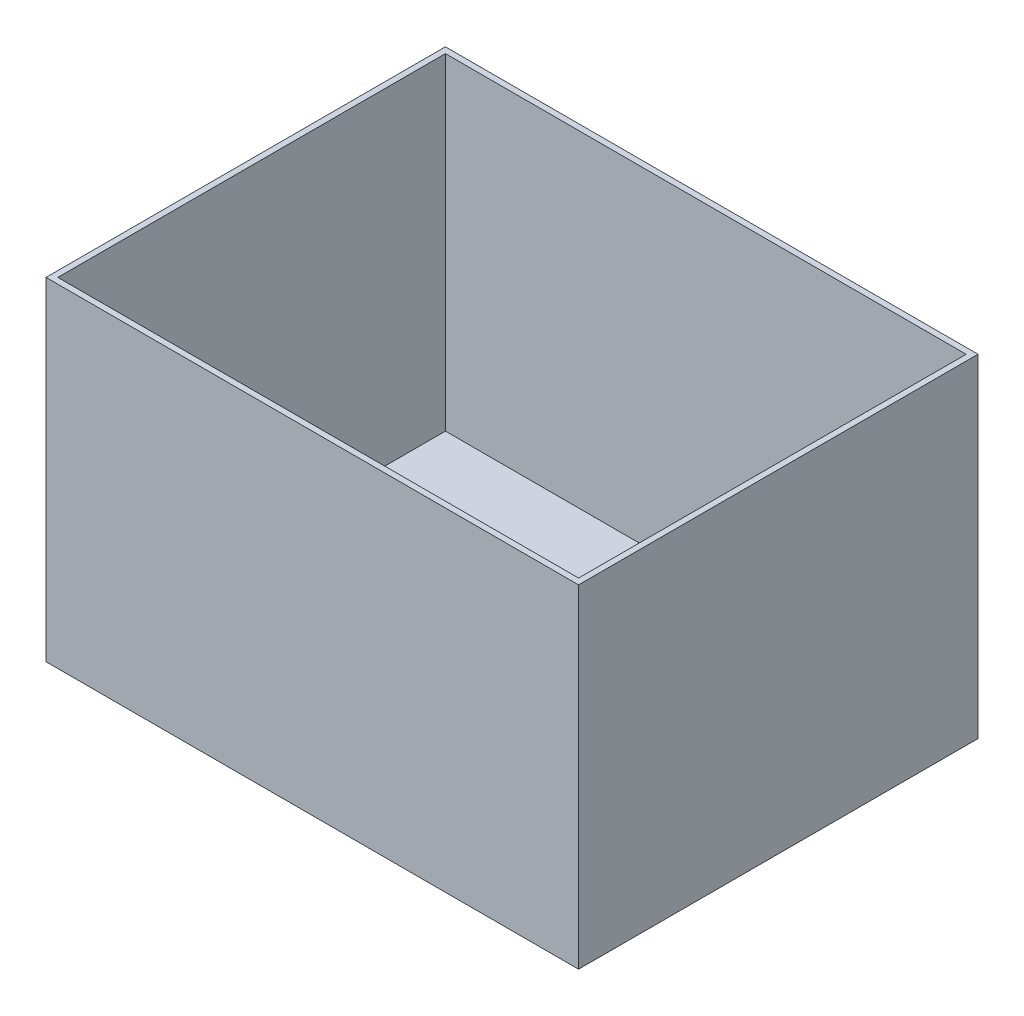
SolidWorks part; units mm, degrees
ref_plane "Alzado" through (0, 0, 0) normal (0, 0, 1) x (1, 0, 0)
ref_plane "Planta" through (0, 0, 0) normal (0, 1, 0) x (1, 0, 0)
ref_plane "Vista lateral" through (0, 0, 0) normal (1, 0, 0) x (0, 0, -1)
sketch "Croquis1" plane through (0, 0, 0) normal (0, 0, 1) x (1, 0, 0)
  line L1 (-180, 112.5) -> (180, 112.5)
  line L2 (-180, 112.5) -> (-180, -112.5)
  line L3 (-180, -112.5) -> (180, -112.5)
  line L4 (180, 112.5) -> (180, -112.5)
  line L5 (-180, 112.5) -> (180, -112.5) construction
  line L6 (-180, -112.5) -> (180, 112.5) construction
  point P0 (0, 0)
extrude "Saliente-Extruir1" add sketch "Croquis1" along normal blind 135 and the other way blind 135
shell "Vaciado1" thickness 4 removed face at (0, 112.5, 0)
sketch "Croquis2" plane through (0, 0, 135) normal (0, 0, 1) x (1, 0, 0)
  line L0 (180, -112.5) -> (180, 112.5) construction
  line L1 (-180, 112.5) -> (180, 112.5)
  line L2 (-180, 112.5) -> (-180, 108.5)
  line L3 (-180, 108.5) -> (180, 108.5)
  line L4 (180, 112.5) -> (180, 108.5)
extrude "Saliente-Extruir2" [suppressed] add sketch "Croquis2" against normal up to surface (270 mm away)
